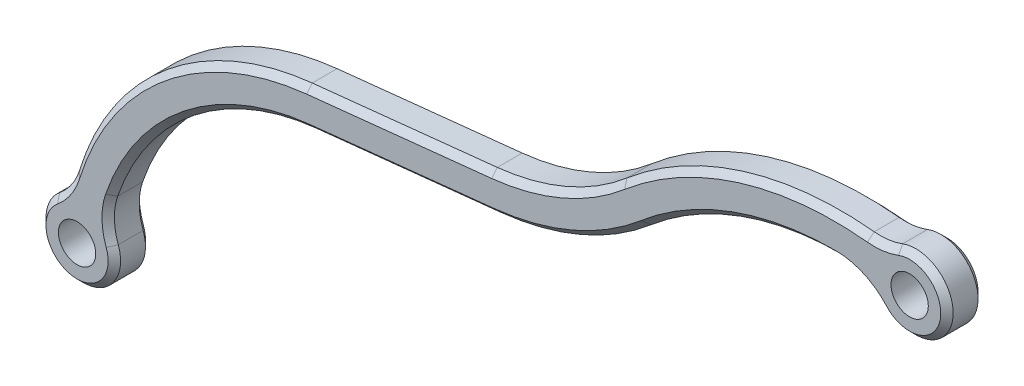
SolidWorks part; units mm, degrees
ref_plane "Спереди" through (0, 0, 0) normal (0, 0, 1) x (1, 0, 0)
ref_plane "Сверху" through (0, 0, 0) normal (0, 1, 0) x (1, 0, 0)
ref_plane "Справа" through (0, 0, 0) normal (1, 0, 0) x (0, 0, -1)
other "Configuration Table"
sketch "Sketch1" plane through (0, 0, 0) normal (0, 0, 1) x (1, 0, 0)
  line L0 (-54.4883, 1.7083) -> (-63.9363, 0.7152) construction
  line L1 (-54.4883, 1.7083) -> (-63.9363, 0.7152) construction
  line L2 (-65.383, -1.297) -> (-50.4992, 0.2674)
  circle A0 centre (-83.9505, -19.9121) radius 1.5 construction
  circle A1 centre (-83.9505, -19.9121) radius 1.5
  circle A2 centre (-17, 9.9282) radius 1.5 construction
  circle A3 centre (-17, 9.9282) radius 1.5
  circle A4 centre (-83.9505, -19.9121) radius 3
  circle A5 centre (-17, 9.9282) radius 3
  arc A6 (-12.8452, 4.492) -> (-12.8452, 1.508) centre (-13, 3) ccw construction
  arc A7 (-12.8452, 4.492) -> (-12.8452, 1.508) centre (-13, 3) ccw construction
  arc A9 (-83.3396, -17.8158) -> (-65.383, -1.297) centre (-63.2448, -21.6405) cw
  arc A10 (-50.4992, 0.2674) -> (-39.2623, 5.0886) centre (-52.6577, 20.804) ccw
  arc A11 (-39.2623, 5.0886) -> (-19.139, 10.7644) centre (-23.0284, -13.9569) cw
  point P13 (-82.7767, -18.0733)
  point P21 (-79.7139, -11.5517)
  point P23 (-81.0494, -7.9369)
  point P24 (-66.552, -2.1925)
  point P25 (-47.69, 0)
  point P26 (-18.5, 11.4282)
  point P27 (-38.9183, 6.3499)
  point P28 (-50.4992, 0.2674)
  point P29 (-34.8478, 7.7258)
  point P30 (-19.139, 10.7644)
  point P31 (-39.2623, 5.0886)
  point P32 (0, 0)
  point P33 (-81.0568, -12.9135)
  point P34 (-82.8914, -17.9586)
  point P35 (-83.3396, -17.8158)
  dimension "D1" = 6
  dimension "D2" = 6
extrude "Boss-Extrude1" add sketch "Sketch1" along normal blind 3 contours A4 A1 | A5 A3 region at (-16.5387, 12.8066, 0) region at (-81.6367, -18.1389, 0)
sketch "Sketch2" plane through (0, 0, 0) normal (0, 0, 1) x (1, 0, 0)
  line L0 (-65.383, -1.297) -> (-50.4992, 0.2674) construction
  line L1 (-65.383, -1.297) -> (-50.4992, 0.2674)
  arc A0 (-19.139, 10.7644) -> (-39.2623, 5.0886) centre (-23.0284, -13.9569) ccw construction
  arc A1 (-50.4992, 0.2674) -> (-39.2623, 5.0886) centre (-52.6577, 20.804) ccw construction
  arc A2 (-65.383, -1.297) -> (-83.3396, -17.8158) centre (-63.2448, -21.6405) ccw construction
  arc A3 (-18.8959, 10.7249) -> (-39.2623, 5.0886) centre (-23.0284, -13.9569) ccw
  arc A4 (-50.4992, 0.2674) -> (-39.2623, 5.0886) centre (-52.6577, 20.804) ccw
  arc A5 (-65.383, -1.297) -> (-83.3396, -17.8158) centre (-63.2448, -21.6405) ccw
  point P5 (-18.8959, 10.7249)
extrude "Extrude-Thin1" add sketch "Sketch2" along normal blind 3 thin thin type mid plane wall 3
fillet "Fillet1" radius 5 4 edges at (-84.7063, -17.0089, 1.5) (-81.8095, -17.8108, 1.5) (-19.9468, 9.3658, 1.5) (-18.9047, 12.246, 1.5)
chamfer "Chamfer1" distance 0.5 angle 45 28 edges at (-31.1067, 8.138, 0) (-43.9243, 0.4487, 0) (-57.7843, -2.0066, 0) (-75.0623, -6.8195, 0) (-30.9252, 11.3657, 0) (-81.4502, -17.1934, 0) (-45.1071, 3.2057, 0) (-84.7375, -22.8071, 0) (-58.0979, 0.977, 0) (-84.8606, -16.5059, 0) (-77.1954, -4.6867, 0) (-31.1067, 8.138, 3) (-43.9243, 0.4487, 3) (-57.7843, -2.0066, 3) (-75.0623, -6.8195, 3) (-30.9252, 11.3657, 3) (-81.4502, -17.1934, 3) (-45.1071, 3.2057, 3) (-84.7375, -22.8071, 3) (-58.0979, 0.977, 3) (-84.8606, -16.5059, 3) (-77.1954, -4.6867, 3) (-20.8969, 9.1322, 0) (-14.0837, 9.2244, 0) (-19.1882, 12.4496, 0) (-20.8969, 9.1322, 3) (-14.0837, 9.2244, 3) (-19.1882, 12.4496, 3)
